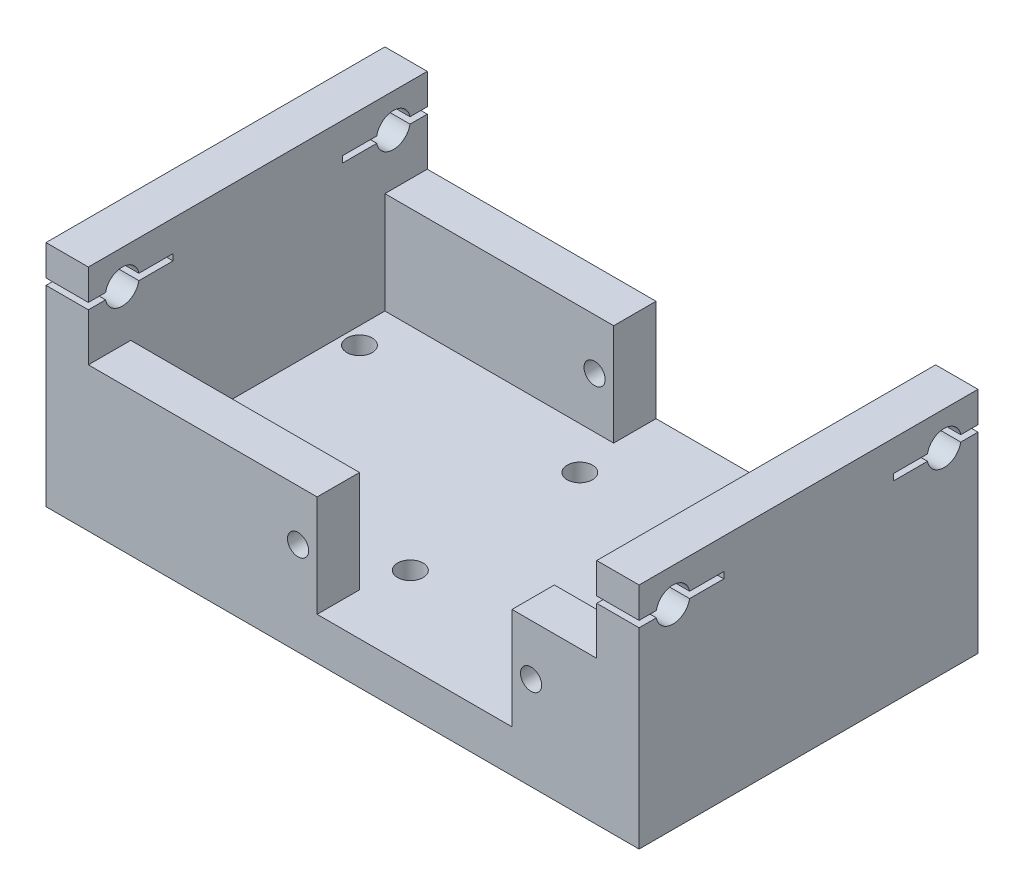
SolidWorks part; units mm, degrees
ref_plane "Front Plane" through (0, 0, 0) normal (0, 0, 1) x (1, 0, 0)
ref_plane "Top Plane" through (0, 0, 0) normal (0, 1, 0) x (1, 0, 0)
ref_plane "Right Plane" through (0, 0, 0) normal (1, 0, 0) x (0, 0, -1)
sketch "Sketch1" plane through (0, 0, 0) normal (0, 1, 0) x (1, 0, 0)
  line L1 (-35, -20) -> (35, -20)
  line L2 (-35, -20) -> (-35, 20)
  line L3 (-35, 20) -> (35, 20)
  line L4 (35, -20) -> (35, 20)
  line L5 (-35, -20) -> (35, 20) construction
  line L6 (-35, 20) -> (35, -20) construction
  point P0 (0, 0)
  dimension "D1" = 70
  dimension "D2" = 40
extrude "Boss-Extrude1" add sketch "Sketch1" along normal blind 5
sketch "Sketch2" plane through (0, 5, 0) normal (0, 1, 0) x (1, 0, 0)
  line L0 (-3, -20) -> (-3, -15)
  line L1 (-35, -20) -> (35, -20) construction
  line L2 (-3, -15) -> (-30, -15)
  line L3 (-35, 20) -> (-35, -20) construction
  line L4 (-30, -15) -> (-30, 15)
  line L6 (-30, 15) -> (-3, 15)
  line L7 (-3, 15) -> (-3, 20)
  line L8 (35, 20) -> (-35, 20) construction
  line L9 (-3, 20) -> (-35, 20)
  line L10 (-35, 20) -> (-35, -20)
  line L11 (-35, -20) -> (-3, -20)
  line L12 (20, -15) -> (30, -15)
  line L13 (35, -20) -> (35, 20) construction
  line L14 (30, -15) -> (30, 15)
  line L15 (30, 15) -> (20, 15)
  line L16 (20, 15) -> (20, 20)
  line L17 (20, 20) -> (35, 20)
  line L18 (35, 20) -> (35, -20)
  line L19 (35, -20) -> (20, -20)
  line L20 (20, -20) -> (20, -15)
  dimension "D1" = 32
  dimension "D2" = 5
  dimension "D3" = 30
  dimension "D4" = 5
  dimension "D5" = 5
  dimension "D6" = 15
  dimension "D9" = 5
extrude "Boss-Extrude2" add sketch "Sketch2" along normal blind 12
sketch "Sketch3" plane through (0, 17, 0) normal (0, 1, 0) x (1, 0, 0)
  line L0 (35, 20) -> (20, 20) construction
  line L1 (35, -20) -> (30, -20)
  line L2 (35, -20) -> (35, 20)
  line L3 (35, 20) -> (30, 20)
  line L4 (30, -20) -> (30, 20)
  line L5 (30, 15) -> (30, -15) construction
  line L6 (-35, -20) -> (-3, -20) construction
  line L7 (-35, 20) -> (-30, 20)
  line L8 (-35, 20) -> (-35, -20)
  line L9 (-35, -20) -> (-30, -20)
  line L10 (-30, 20) -> (-30, -20)
  line L11 (-30, -15) -> (-30, 15) construction
extrude "Boss-Extrude3" add sketch "Sketch3" along normal blind 10
sketch "Sketch5" plane through (-35, 0, 0) normal (-1, 0, 0) x (0, 0, 1)
  line L0 (-20, 27) -> (20, 27) construction
  line L1 (20, 27) -> (20, 0) construction
  line L2 (0, -2.75) -> (0, 2.75) construction
  circle A0 centre (16, 23) radius 2
  circle A1 centre (-16, 23) radius 2
  dimension "D1" = 4
  dimension "D2" = 4
  dimension "D3" = 4
extrude "Cut-Extrude1" cut sketch "Sketch5" against normal through all
sketch "Sketch7" plane through (0, 0, 15) normal (0, 0, -1) x (-1, 0, 0)
  line L0 (-20, 17) -> (-20, 5) construction
  line L1 (3, 17) -> (3, 5) construction
  line L2 (3, 17) -> (30, 17) construction
  line L3 (-30, 17) -> (-20, 17) construction
  circle A0 centre (-22.25, 11) radius 1.25
  circle A1 centre (5.25, 11) radius 1.25
  dimension "D1" = 2.5
  dimension "D2" = 2.25
  dimension "D4" = 6
  dimension "D5" = 2.5
  dimension "D6" = 6
  dimension "D3" = 2.25
extrude "Cut-Extrude3" cut sketch "Sketch7" against normal through all and the other way through all
sketch "Sketch8" plane through (-35, 0, 0) normal (-1, 0, 0) x (0, 0, 1)
  line L0 (20, 27) -> (20, 0) construction
  line L1 (20, 23.375) -> (10, 23.375)
  line L2 (20, 23.375) -> (20, 22.625)
  line L3 (20, 22.625) -> (10, 22.625)
  line L4 (-20, 23.375) -> (-20, 22.625)
  line L5 (-20, 27) -> (-20, 0) construction
  line L6 (10, 23.375) -> (10, 22.625)
  line L7 (-10, 23.375) -> (-10, 22.625)
  line L8 (-10, 23.375) -> (-20, 23.375)
  line L9 (-10, 22.625) -> (-20, 22.625)
  circle A0 centre (16, 23) radius 2 construction
  dimension "D1" = 0.75
  dimension "D2" = 0.375
  dimension "D3" = 10
  dimension "D4" = 10
extrude "Cut-Extrude4" cut sketch "Sketch8" against normal through all
sketch "Sketch9" plane through (0, 0, 0) normal (0, -1, 0) x (-1, 0, 0)
  line L0 (35, -20) -> (-35, -20) construction
  line L1 (23.5, -20) -> (19.5, -20)
  line L2 (23.5, -20) -> (23.5, 20)
  line L3 (23.5, 20) -> (19.5, 20)
  line L4 (19.5, -20) -> (19.5, 20)
  line L5 (-35, 20) -> (35, 20) construction
  line L6 (0, -20) -> (0, 19.3326) construction
  line L7 (15, -20) -> (11, -20)
  line L8 (15, -20) -> (15, 20)
  line L9 (15, 20) -> (11, 20)
  line L10 (11, -20) -> (11, 20)
  dimension "D1" = 4
  dimension "D2" = 4
  dimension "D3" = 4.5
  dimension "D4" = 15
extrude "Boss-Extrude4" [suppressed] add sketch "Sketch9" along normal blind 20
sketch "Sketch11" plane through (-1.6583, 0, 0) normal (-1, 0, 0) x (0, 0, 1)
  circle A1 centre (11.5, -14.5) radius 1.25
  circle A2 centre (-16, -14.5) radius 1.25
  circle A3 centre (-16, -7) radius 1.25
  circle A4 centre (11.5, -7) radius 1.25
  dimension "D1" = 2.5
  dimension "D2" = 2.5
  dimension "D3" = 2.5
  dimension "D4" = 7.5
  dimension "D5" = 2.5
  dimension "D6" = 7.5
  dimension "D7" = 27.5
extrude "Cut-Extrude5" [suppressed] cut sketch "Sketch11" against normal through all and the other way through all
sketch "Sketch12" plane through (0, 0, 0) normal (0, -1, 0) x (1, 0, 0)
  line L0 (-35, -20) -> (-35, 20) construction
  line L2 (35, -20) -> (-35, -20) construction
  line L5 (-35, 20) -> (35, 20) construction
  circle A0 centre (-28, 10) radius 1.5
  circle A1 centre (-28, -10) radius 1.5
  circle A2 centre (-2, 10) radius 1.5
  circle A3 centre (-2, -10) radius 1.5
  point P12 (0, 0)
  point P18 (0, 0)
  point P19 (0, 0)
  point P20 (0, 0)
  dimension "D1" = 3
  dimension "D2" = 3
  dimension "D3" = 7
  dimension "D5" = 7
  dimension "D6" = 10
  dimension "D7" = 3
  dimension "D8" = 33
  dimension "D9" = 10
  dimension "D10" = 3
extrude "Cut-Extrude6" cut sketch "Sketch12" against normal through all
